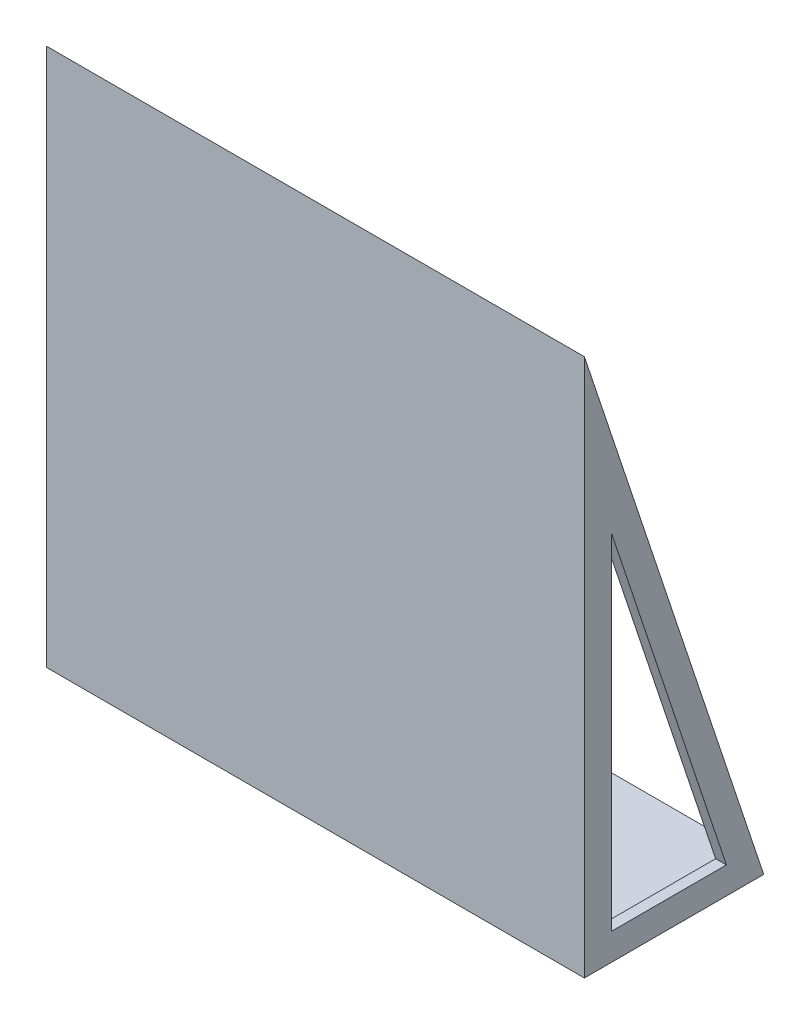
SolidWorks part; units mm, degrees
ref_plane "Front Plane" through (0, 0, 0) normal (0, 0, 1) x (1, 0, 0)
ref_plane "Top Plane" through (0, 0, 0) normal (0, 1, 0) x (1, 0, 0)
ref_plane "Right Plane" through (0, 0, 0) normal (1, 0, 0) x (0, 0, -1)
sketch "Sketch1" plane through (0, 0, 0) normal (0, 0, 1) x (1, 0, 0)
  line L1 (-150, 150) -> (150, 150)
  line L2 (-150, 150) -> (-150, -150)
  line L3 (-150, -150) -> (150, -150)
  line L4 (150, 150) -> (150, -150)
  line L5 (-150, 150) -> (150, -150) construction
  line L6 (-150, -150) -> (150, 150) construction
  point P0 (0, 0)
  dimension "D1" = 300
  dimension "D2" = 300
extrude "Boss-Extrude1" add sketch "Sketch1" against normal blind 100
sketch "Sketch3" plane through (-150, 0, 0) normal (-1, 0, 0) x (0, 0, 1)
  line L0 (-100, 150) -> (-100, -150)
  line L1 (-100, -150) -> (0, 150)
  line L2 (0, 150) -> (-100, 150)
sketch "Sketch4" plane through (0, 150, 0) normal (0, 1, 0) x (1, 0, 0)
  line L0 (150, 100) -> (-150, 100) construction
  line L1 (-144, 100) -> (144, 100)
  line L2 (-144, 100) -> (-144, 6)
  line L3 (-144, 6) -> (144, 6)
  line L4 (144, 100) -> (144, 6)
  line L5 (-150, 0) -> (-150, 100) construction
  line L6 (150, 100) -> (150, 0) construction
  line L7 (150, 0) -> (-150, 0) construction
  dimension "D1" = 6
  dimension "D2" = 6
  dimension "D3" = 6
extrude "Cut-Extrude1" cut sketch "Sketch4" against normal blind 290
extrude "Cut-Extrude2" cut sketch "Sketch3" against normal blind 309.1
sketch "Sketch5" plane through (-150, 0, 0) normal (-1, 0, 0) x (0, 0, 1)
  line L0 (-15, -135) -> (-15, 57.5658)
  line L1 (-15, 57.5658) -> (-79.1886, -135)
  line L2 (-79.1886, -135) -> (-15, -135)
  line L3 (0, 150) -> (0, -150) construction
  line L4 (-100, -150) -> (0, -150) construction
  line L5 (-100, -150) -> (0, 150) construction
  point P7 (0, 0)
  point P8 (-10, 8.9888)
  point P9 (-73.8395, -140)
  point P10 (-10, 65.7161)
  point P11 (0, 0)
  point P12 (0, 0)
  dimension "D1" = 15
  dimension "D2" = 15
  dimension "D3" = 15
extrude "Cut-Extrude3" cut sketch "Sketch5" against normal blind 309.1
